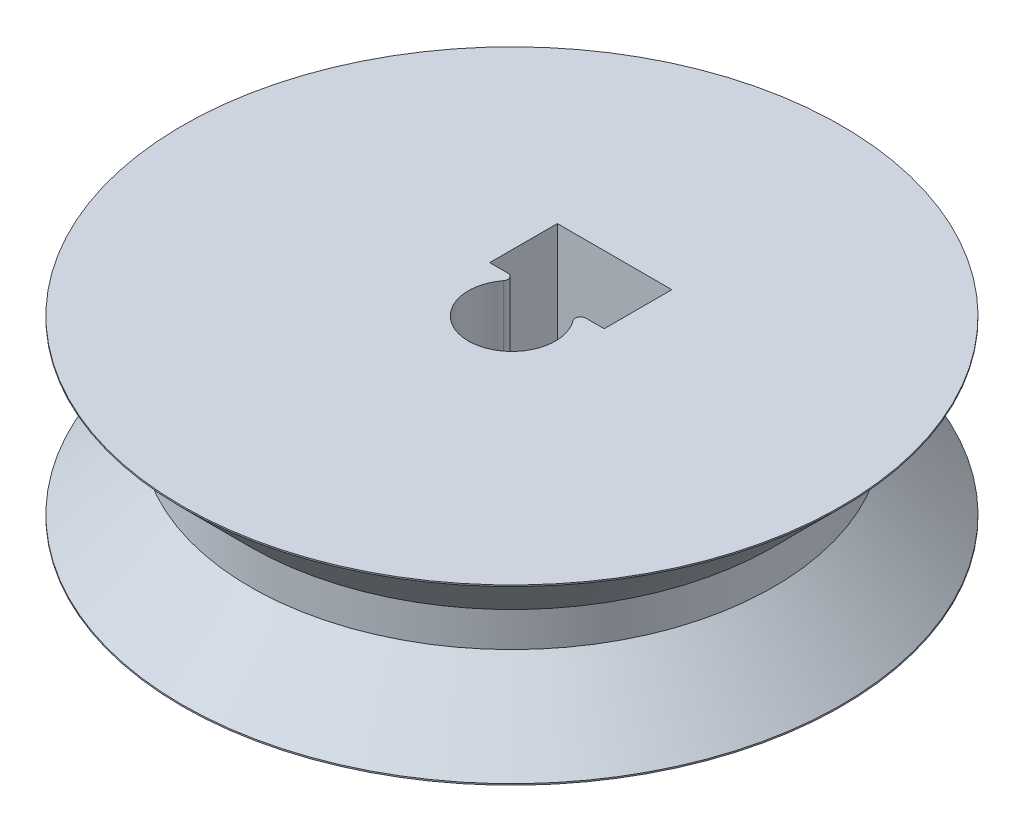
SolidWorks part; units mm, degrees
ref_plane "Front Plane" through (0, 0, 0) normal (0, 0, 1) x (1, 0, 0)
ref_plane "Top Plane" through (0, 0, 0) normal (0, 1, 0) x (1, 0, 0)
ref_plane "Right Plane" through (0, 0, 0) normal (1, 0, 0) x (0, 0, -1)
sketch "Sketch7" plane through (0, 0, 0) normal (0, 0, 1) x (1, 0, 0)
  line L0 (0, 0) -> (24.13, 0)
  line L1 (24.13, 0) -> (24.13, 0.1)
  line L2 (24.13, 0.1) -> (19.15, 5.08)
  line L3 (19.15, 5.08) -> (19.15, 7.62)
  line L4 (19.15, 7.62) -> (24.13, 12.6)
  line L5 (24.13, 12.6) -> (24.13, 12.7)
  line L6 (24.13, 12.7) -> (0, 12.7)
  line L7 (0, 12.7) -> (0, 0)
  line L8 (24.13, 12.7) -> (24.13, 0) construction
  line L9 (19.15, 6.35) -> (24.13, 6.35) construction
  dimension "D1" = 12.7
  dimension "D2" = 0.1
  dimension "D3" = 45
  dimension "D4" = 2.54
  dimension "D5" = 24.13
revolve "Revolve1" add sketch "Sketch7" angle 360 about L7
sketch "Sketch8" plane through (0, 12.7, 0) normal (0, 1, 0) x (1, 0, 0)
  line L0 (-1.8994, 2.5635) -> (1.8994, 2.5635)
  line L1 (0, 2.5635) -> (0, -3.1905) construction
  arc A0 (-1.8994, 2.5635) -> (1.8994, 2.5635) centre (0, 0) ccw
  dimension "D1" = 6.381
  dimension "D2" = 5.754
extrude "Cut-Extrude2" cut sketch "Sketch8" against normal through all
sketch "Sketch9" plane through (0, 12.7, 0) normal (0, 1, 0) x (1, 0, 0)
  line L1 (-4.191, 2.5635) -> (4.191, 2.5635)
  line L2 (-4.191, 2.5635) -> (-4.191, 7.5165)
  line L3 (-4.191, 7.5165) -> (4.191, 7.5165)
  line L4 (4.191, 2.5635) -> (4.191, 7.5165)
  line L6 (1.8994, 2.5635) -> (-1.8994, 2.5635) construction
  point P6 (0, 7.5165)
  dimension "D1" = 8.382
  dimension "D2" = 4.953
extrude "Cut-Extrude3" cut sketch "Sketch9" against normal through all
fillet "Fillet2" radius 0.3969 2 edges at (1.8994, 6.35, -2.5635) (-1.8994, 6.35, -2.5635)
hole_wizard "#8-32 Tapped Hole1" positions "Sketch13" profile "Sketch14" tap size "#8-32" standard "ANSI Inch" end condition through all
sketch "Sketch13" plane through (0, 0, -2.5635) normal (0, 0, -1) x (-1, 0, 0)
  point P0 (0, 6.1533)
sketch "Sketch14" plane through (0, 6.1533, -2.5635) normal (1, 0, 0) x (0, -1, 0)
  line L0 (0, 0) -> (0, 21.5665)
  line L1 (0, 21.5665) -> (1.7272, 21.5665)
  line L2 (1.7272, 21.5665) -> (1.7272, 0)
  line L5 (1.7272, 0) -> (0, 0)
  line L11 (0, -6.35) -> (0, 107.95) construction
  dimension "Thread Major Dia." = 3.4544
  dimension "Thru Tap Drill Depth" = 21.5665
ref_plane "Plane2" through (0, 0, -19.15) normal (0, 0, -1) x (-1, 0, 0)
sketch "Sketch15" plane through (0, 0, -19.15) normal (0, 0, -1) x (-1, 0, 0)
  line L0 (0, 7.62) -> (0, 5.08) construction
  line L1 (19.15, 5.08) -> (-19.15, 5.08) construction
  line L2 (0, 5.08) -> (0, 7.62) construction
  line L3 (19.15, 7.62) -> (-19.15, 7.62) construction
  circle A0 centre (0, 6.35) radius 3.429
  dimension "D1" = 6.858
extrude "Cut-Extrude4" cut sketch "Sketch15" against normal blind 6.096 and the other way through all contours A0
sketch "Sketch16" plane through (0, 0, -19.15) normal (0, 0, -1) x (-1, 0, 0)
  line L0 (12.7, 12.7) -> (12.7, 0) construction
  line L2 (24.13, 12.7) -> (-24.13, 12.7) construction
  line L3 (-24.13, 0) -> (24.13, 0) construction
  line L4 (0, 12.6) -> (0, 7.62) construction
  circle A0 centre (12.7, 6.35) radius 1.27
  circle A1 centre (12.7, 6.35) radius 2.54
  dimension "D1" = 2.54
  dimension "D3" = 5.08
  dimension "D2" = 12.7
extrude "Cut-Extrude6" cut sketch "Sketch16" against normal through all from surface contours L0 A0 | A0 L0 region at (-13.239, 6.35, -19.15) region at (-12.161, 6.35, -19.15) starting at plane "Front Plane"
extrude "Cut-Extrude7" cut sketch "Sketch16<3>" along normal through all from surface contours L0 A1 A0 | A1 L0 A0 | A0 L0 | L0 A0 region at (-14.4559, 8.1059, -19.15) region at (-12.6432, 8.255, -19.15) region at (-13.239, 6.35, -19.15) region at (-12.161, 6.35, -19.15) starting at plane "Front Plane"
sketch "Sketch16<3>" plane through (0, 0, -19.15) normal (0, 0, -1) x (-1, 0, 0) same geometry as "Sketch16"
